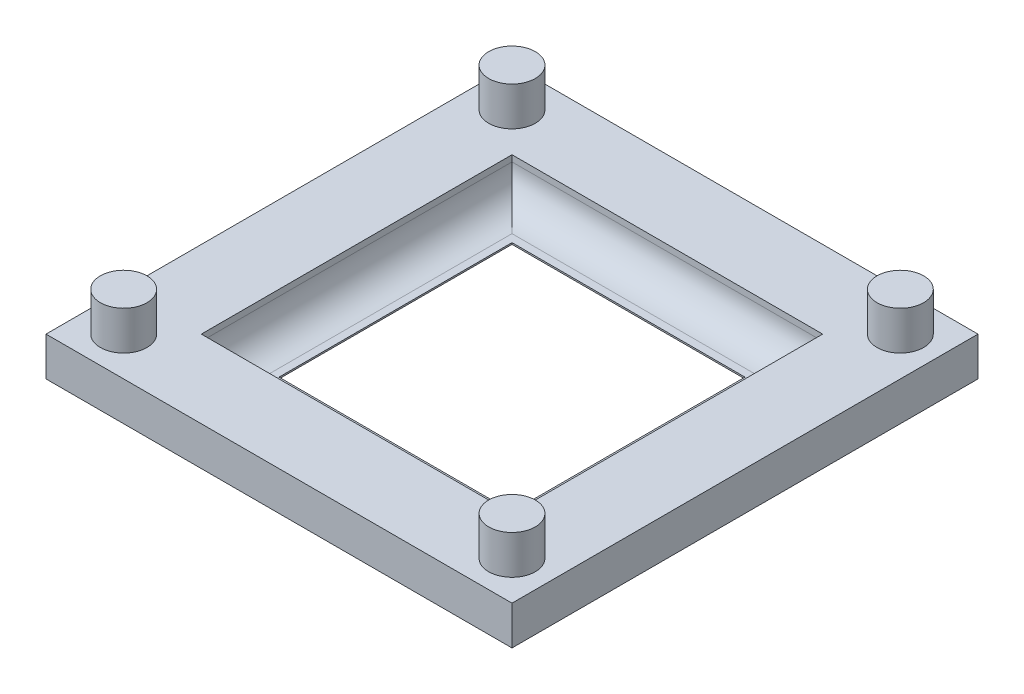
SolidWorks part; units mm, degrees
ref_plane "Front Plane" through (0, 0, 0) normal (0, 0, 1) x (1, 0, 0)
ref_plane "Top Plane" through (0, 0, 0) normal (0, 1, 0) x (1, 0, 0)
ref_plane "Right Plane" through (0, 0, 0) normal (1, 0, 0) x (0, 0, -1)
sketch "Sketch1" plane through (0, 0, 0) normal (0, 1, 0) x (1, 0, 0)
  line L1 (-15, -15) -> (15, -15)
  line L2 (-15, -15) -> (-15, 15)
  line L3 (-15, 15) -> (15, 15)
  line L4 (15, -15) -> (15, 15)
  line L5 (-15, -15) -> (15, 15) construction
  line L6 (-15, 15) -> (15, -15) construction
  line L7 (-10, -10) -> (10, -10)
  line L8 (-10, -10) -> (-10, 10)
  line L9 (-10, 10) -> (10, 10)
  line L10 (10, -10) -> (10, 10)
  line L11 (-10, -10) -> (10, 10) construction
  line L12 (-10, 10) -> (10, -10) construction
  line L13 (-7.5, -7.5) -> (7.5, -7.5)
  line L14 (-7.5, -7.5) -> (-7.5, 7.5)
  line L15 (-7.5, 7.5) -> (7.5, 7.5)
  line L16 (7.5, -7.5) -> (7.5, 7.5)
  line L17 (-7.5, -7.5) -> (7.5, 7.5) construction
  line L18 (-7.5, 7.5) -> (7.5, -7.5) construction
  point P0 (0, 0)
  point P6 (0, 0)
  point P11 (0, 0)
  dimension "D1" = 30
  dimension "D2" = 30
  dimension "D3" = 15
  dimension "D4" = 15
extrude "Boss-Extrude3" add sketch "Sketch1" along normal blind 0.1 contours L7 L10 L9 L8 L16 L13 L14 L15 region at (-9.7172, 0, 0)
extrude "Boss-Extrude4" add sketch "Sketch1<5>" along normal blind 2.5 contours L1 L4 L3 L2 L10 L7 L8 L9 region at (-14.5757, 0, 0)
sketch "Sketch1<5>" plane through (0, 0, 0) normal (0, 1, 0) x (1, 0, 0) same geometry as "Sketch1"
fillet "Fillet2" radius 2 4 edges at (0, 0.1, 10) (0, 0.1, -10) (10, 0.1, 0) (-10, 0.1, 0)
sketch "Sketch2" plane through (0, 2.5, 0) normal (0, 1, 0) x (1, 0, 0)
  line L0 (-15, 15) -> (-10, 10)
  line L1 (15, 15) -> (10, 10)
  line L2 (10, -10) -> (15, -15)
  line L3 (-10, -10) -> (-15, -15)
  circle A0 centre (-12.5, 12.5) radius 1.5
  circle A1 centre (12.5, 12.5) radius 1.5
  circle A2 centre (-12.5, -12.5) radius 1.5
  circle A3 centre (12.5, -12.5) radius 1.5
extrude "Boss-Extrude5" add sketch "Sketch2" along normal blind 2.5 contours L2 A3 | L2 A3 | L1 A1 | L1 A1 | L0 A0 | L0 A0 | L3 A2 | L3 A2 region at (-12.0498, 2.5, -12.9502) region at (-12.9502, 2.5, -12.0498) region at (12.9502, 2.5, -12.0498) region at (12.0498, 2.5, -12.9502) region at (12.9502, 2.5, 12.0498) region at (12.0498, 2.5, 12.9502) region at (-12.0498, 2.5, 12.9502) region at (-12.9502, 2.5, 12.0498)
